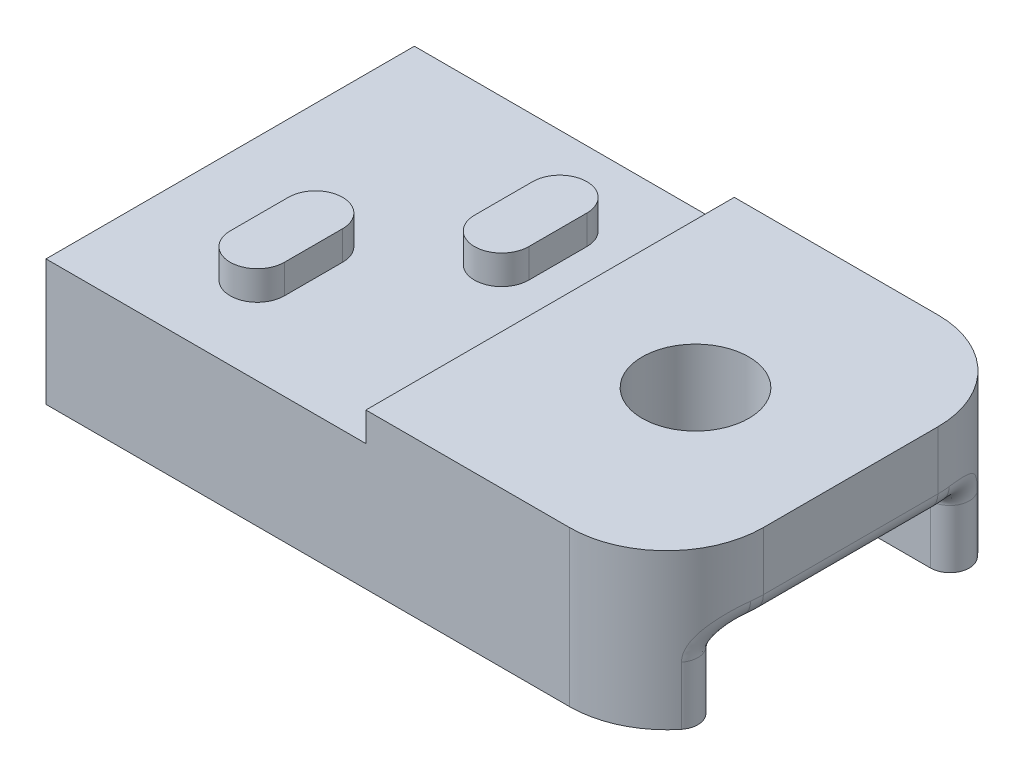
SolidWorks part; units mm, degrees
ref_plane "Front Plane" through (0, 0, 0) normal (0, 0, 1) x (1, 0, 0)
ref_plane "Top Plane" through (0, 0, 0) normal (0, 1, 0) x (1, 0, 0)
ref_plane "Right Plane" through (0, 0, 0) normal (1, 0, 0) x (0, 0, -1)
sketch "Sketch1" plane through (0, 0, 0) normal (0, 1, 0) x (1, 0, 0)
  line L1 (-16, 9.5) -> (16, 9.5)
  line L2 (-16, 9.5) -> (-16, -9.5)
  line L3 (-16, -9.5) -> (16, -9.5)
  line L4 (16, 9.5) -> (16, -9.5)
  line L5 (-16, 9.5) -> (16, -9.5) construction
  line L6 (-16, -9.5) -> (16, 9.5) construction
  point P0 (0, 0)
  dimension "D1" = 19
  dimension "D2" = 32
extrude "Boss-Extrude1" add sketch "Sketch1" along normal blind 8
sketch "Sketch2" plane through (0, 8, 0) normal (0, 1, 0) x (1, 0, 0)
  line L0 (-55, 0) -> (55, 0) construction
  line L1 (16, -9.5) -> (16, 9.5) construction
  circle A0 centre (8, 0) radius 2.75
  dimension "D1" = 5.5
  dimension "D2" = 8
extrude "Cut-Extrude1" cut sketch "Sketch2" against normal up to next
sketch "Sketch4" plane through (0, 8, 0) normal (0, 1, 0) x (1, 0, 0)
  line L0 (0, -55) -> (0, 55) construction
  line L1 (-16, 9.5) -> (0.5, 9.5)
  line L2 (-16, 9.5) -> (-16, -9.5)
  line L3 (-16, -9.5) -> (0.5, -9.5)
  line L4 (0.5, 9.5) -> (0.5, -9.5)
  line L5 (-4, 5) -> (-4, 2) construction
  line L6 (-2.6, 5) -> (-2.6, 2)
  line L7 (-5.4, 5) -> (-5.4, 2)
  line L8 (-9.6, -2) -> (-9.6, -5) construction
  line L9 (-8.2, -2) -> (-8.2, -5)
  line L10 (-11, -2) -> (-11, -5)
  arc A0 (-2.6, 5) -> (-5.4, 5) centre (-4, 5) ccw
  arc A1 (-5.4, 2) -> (-2.6, 2) centre (-4, 2) ccw
  arc A2 (-8.2, -2) -> (-11, -2) centre (-9.6, -2) ccw
  arc A3 (-11, -5) -> (-8.2, -5) centre (-9.6, -5) ccw
  point P9 (-4, 3.5)
  point P14 (-9.6, -3.5)
  dimension "D4" = 1.4
  dimension "D6" = 1.4
  dimension "D1" = 19
  dimension "D2" = 4.5
  dimension "D3" = 3
  dimension "D5" = 4
  dimension "D7" = 3
  dimension "D8" = 4.5
  dimension "D9" = 9.6
  dimension "D10" = 16.5
extrude "Cut-Extrude2" cut sketch "Sketch4" against normal blind 1.5
fillet "Fillet1" radius 5 2 edges at (16, 4, 9.5) (16, 4, -9.5)
sketch "Sketch5" plane through (0, 0, 0) normal (0, 1, 0) x (1, 0, 0)
  line L0 (-16, 9.5) -> (-16, -9.5) construction
  line L1 (-16, 6) -> (16, 6)
  line L2 (-16, 6) -> (-16, -6)
  line L3 (-16, -6) -> (16, -6)
  line L4 (16, 6) -> (16, -6)
  line L5 (-4.4, 0) -> (4.4, 0) construction
  dimension "D1" = 32
  dimension "D2" = 6
  dimension "D3" = 12
extrude "Cut-Extrude3" cut sketch "Sketch5" along normal blind 4
fillet "Fillet2" radius 1 7 edges at (16, 4, 0) (15.9421, 4, 5.2588) (15.9421, 4, -5.2588) (15.7697, 2, 6) (15.7697, 2, -6) (-0.1152, 4, -6) (-0.1152, 4, 6)
